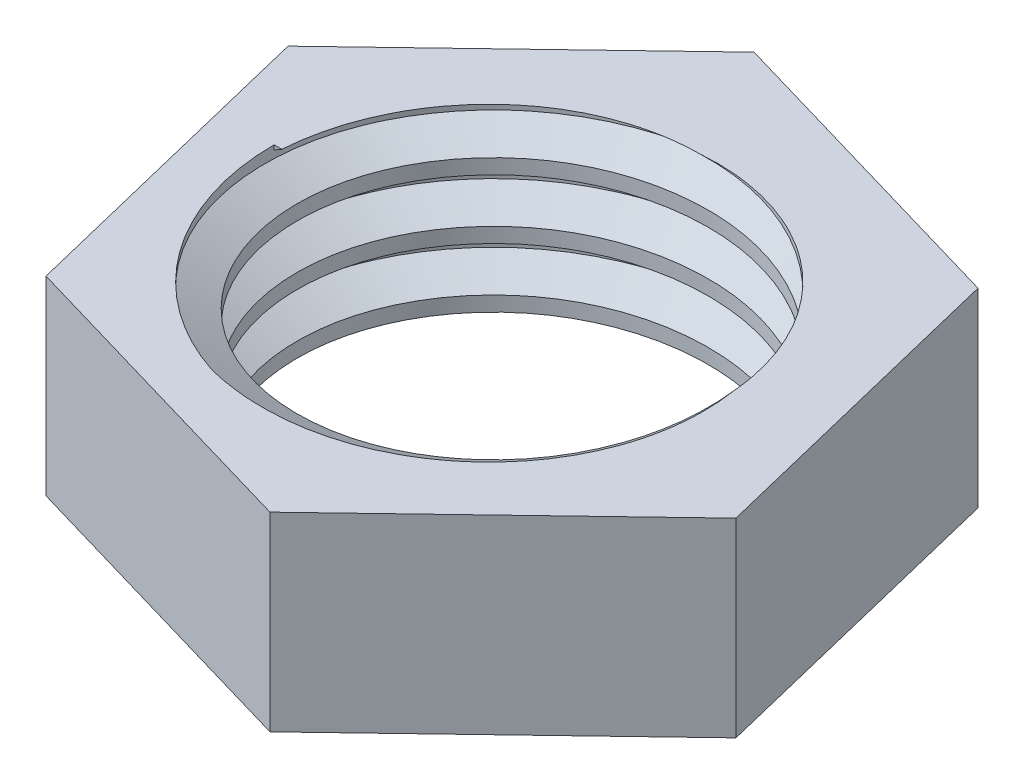
SolidWorks part; units mm, degrees
ref_plane "Front Plane" through (0, 0, 0) normal (0, 0, 1) x (1, 0, 0)
ref_plane "Top Plane" through (0, 0, 0) normal (0, 1, 0) x (1, 0, 0)
ref_plane "Right Plane" through (0, 0, 0) normal (1, 0, 0) x (0, 0, -1)
sketch "Sketch1" plane through (0, 0, 0) normal (0, 1, 0) x (1, 0, 0)
  line L1 (5.0076, 4.7879) -> (-1.6427, 6.7306)
  line L2 (-1.6427, 6.7306) -> (-6.6503, 1.9427)
  line L3 (-6.6503, 1.9427) -> (-5.0076, -4.7879)
  line L4 (-5.0076, -4.7879) -> (1.6427, -6.7306)
  line L5 (1.6427, -6.7306) -> (6.6503, -1.9427)
  line L6 (6.6503, -1.9427) -> (5.0076, 4.7879)
  circle A1 centre (0, 0) radius 6 construction
  dimension "D1" = 12
extrude "Boss-Extrude1" add sketch "Sketch1" along normal blind 4
sketch "Sketch2" plane through (0, 4, 0) normal (0, 1, 0) x (1, 0, 0)
  circle A0 centre (0, 0) radius 5
extrude "Cut-Extrude1" cut sketch "Sketch2" against normal through all
thread "Thread2" pitch 1.25 method extrude profile "Thread Profile2" start angle 0, offset 1, length 8, pitch 1.25, diameter 10
ref_plane "Plane2" through (-5, 5, 0) normal (0, 0, 1) x (-1, 0, 0)
sketch "Thread Profile2" plane through (-5, 5, 0) normal (0, 0, 1) x (-1, 0, 0)
  line L0 (0, 0) -> (0, 1.25) construction
  line L11 (0, 0) -> (0, 1.0937)
  line L12 (0, 1.0937) -> (-0.6766, 0.7031)
  line L13 (-0.6766, 0.7031) -> (-0.6766, 0.3906)
  line L15 (-0.6766, 0.3906) -> (0, 0)
  line L17 (-0.6766, 0.5469) -> (0, 0.5469) construction
  point P2 (0, 0)
  dimension "Pitch" = 1.25
  dimension "Profile_Angle" = 60
  dimension "Profile_Land" = 0.3125
  dimension "Profile_Height" = 0.6766
sketch "Sketch7" plane through (0, 0, 0) normal (0, -1, 0) x (1, 0, 0)
  circle A0 centre (-8.7275, 7.0288) radius 21.0283
extrude "Cut-Extrude2" cut sketch "Sketch7" along normal through all
sketch "Sketch8" plane through (0, 4, 0) normal (0, 1, 0) x (1, 0, 0)
  circle A0 centre (-10.1137, 5.9354) radius 21.0374
extrude "Cut-Extrude3" cut sketch "Sketch8" along normal through all
